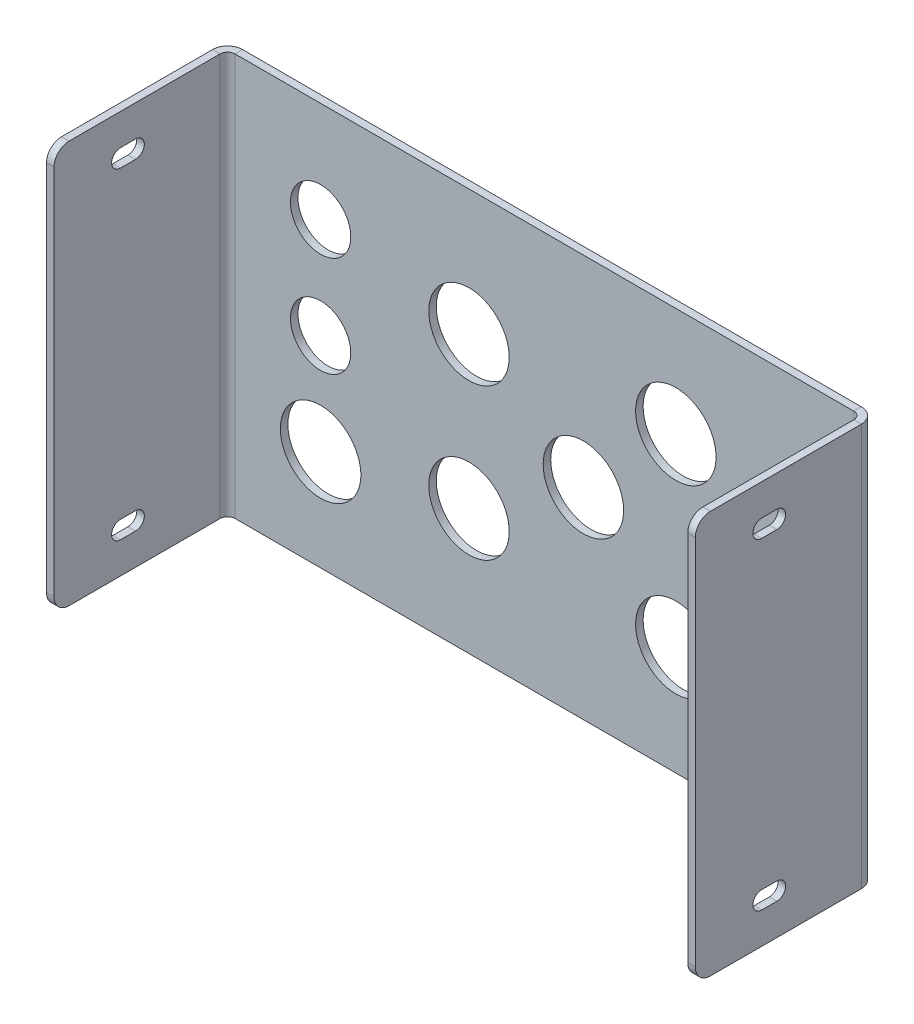
SolidWorks part; units mm, degrees
note: The reader was unsure of these and kept them because the rebuilt part matched: bend radius of "DobradeBase1", "DobradeBase2".
material "Liga 1060"
ref_plane "Plano frontal" through (0, 0, 0) normal (0, 0, 1) x (1, 0, 0)
ref_plane "Plano superior" through (0, 0, 0) normal (0, 1, 0) x (1, 0, 0)
ref_plane "Plano direito" through (0, 0, 0) normal (1, 0, 0) x (0, 0, -1)
sketch "Esboço2" plane through (0, 0, 0) normal (0, 1, 0) x (1, 0, 0)
  line L0 (-63, 0) -> (63, 0)
  line L1 (63, 0) -> (63, -34.5)
  line L2 (-63, 0) -> (-63, -34.5)
  dimension "D1" = 126
  dimension "D2" = 34.5
sheet metal parameters "Chapa metálica1" thickness 1.5 parameters "D1"=1.5
base flange "Flange-base1" sketch "Esboço2" end condition mid plane depth 80 reverse direction no thickness 1.5 reverse thickness direction no bend radius 1.5
bend "DobradeBase1" bend radius 1.5 bend angle 90 parameters "D5"=1
bend "DobradeBase2" bend radius 1.5 bend angle 90 parameters "D5"=2
sketch "Esboço4" plane through (0, 0, -1.5) normal (0, 0, -1) x (-1, 0, 0)
  line L0 (-70.5083, 0) -> (70.5083, 0) construction
  line L2 (64.5, 40) -> (64.5, -40) construction
  line L3 (-64.5, 40) -> (-64.5, -40) construction
  circle A0 centre (44.5, 0) radius 6
  circle A1 centre (44.5, -20) radius 8
  circle A2 centre (44.5, 20) radius 6
  circle A3 centre (15, 15) radius 8
  circle A4 centre (-44.5, 0) radius 8
  circle A5 centre (-26.1246, 18.3754) radius 8
  circle A6 centre (-7.7491, 0) radius 8
  circle A7 centre (-26.1246, -18.3754) radius 8
  circle A8 centre (15, -15) radius 8
  dimension "D1" = 16
  dimension "D2" = 12
  dimension "D3" = 16
  dimension "D4" = 12
  dimension "D5" = 16
  dimension "D6" = 0
  dimension "D11" = 20
  dimension "D7" = 20
  dimension "D8" = 20
  dimension "D9" = 20
  dimension "D10" = 15
  dimension "D13" = 15
  dimension "D12" = 4
extrude "Corte-extrusão1" cut sketch "Esboço4" against normal up to surface (1.5 mm away) normal cut yes up to face at (0, 0, 0)
fillet "Filete1" radius 3 4 edges at (63.75, -40, 34.5) (63.75, 40, 34.5) (-63.75, -40, 34.5) (-63.75, 40, 34.5)
sketch "Esboço5" plane through (-64.5, 0, 0) normal (-1, 0, 0) x (0, 0, 1)
  line L0 (0, 0) -> (34.5, 0) construction
  line L1 (34.5, 37) -> (34.5, -37) construction
  line L2 (-1.5, 40) -> (-1.5, -40) construction
  line L3 (18.3, 32) -> (21.3, 32) construction
  line L4 (18.3, 33.75) -> (21.3, 33.75)
  line L5 (18.3, 30.25) -> (21.3, 30.25)
  line L6 (18.3, -32) -> (21.3, -32) construction
  line L7 (18.3, -32) -> (21.3, -32) construction
  line L8 (18.3, -32) -> (21.3, -32) construction
  line L9 (18.3, -32) -> (21.3, -32) construction
  line L10 (18.3, -30.25) -> (21.3, -30.25)
  line L11 (18.3, -33.75) -> (21.3, -33.75)
  line L12 (1.5, -40) -> (31.5, -40) construction
  line L13 (19.8, 32) -> (19.8, -32) construction
  circle A0 centre (19.8, -32) radius 1.75 construction
  circle A1 centre (19.8, 32) radius 1.75 construction
  arc A2 (18.3, 33.75) -> (18.3, 30.25) centre (18.3, 32) ccw
  arc A3 (21.3, 30.25) -> (21.3, 33.75) centre (21.3, 32) ccw
  circle A4 centre (19.8, -32) radius 1.75 construction
  arc A5 (18.3, -30.25) -> (18.3, -33.75) centre (18.3, -32) ccw
  arc A6 (21.3, -33.75) -> (21.3, -30.25) centre (21.3, -32) ccw
  point P13 (19.8, 32)
  point P24 (19.8, -32)
  dimension "D1" = 3.5
  dimension "D2" = 64
  dimension "D3" = 21.3
  dimension "D4" = 3.5
  dimension "D5" = 3
extrude "Corte-extrusão2" cut sketch "Esboço5" against normal through all normal cut yes
flat pattern "Padrão-Plano1" [suppressed]
sketch "Curva-Linhas1" plane through (0, 0, 0) normal (0, 0, 1) x (1, 0, 0)
  line L0 (65.2671, 40) -> (65.2671, -40) construction
  line L1 (-65.2671, 40) -> (-65.2671, -40) construction
  line L2 (65.2671, 40) -> (65.2671, -40) construction
  line L3 (-65.2671, 40) -> (-65.2671, -40) construction
bend of the flat pattern "Planificar-<DobradeBase1>1"
bend of the flat pattern "Planificar-<DobradeBase2>1"
